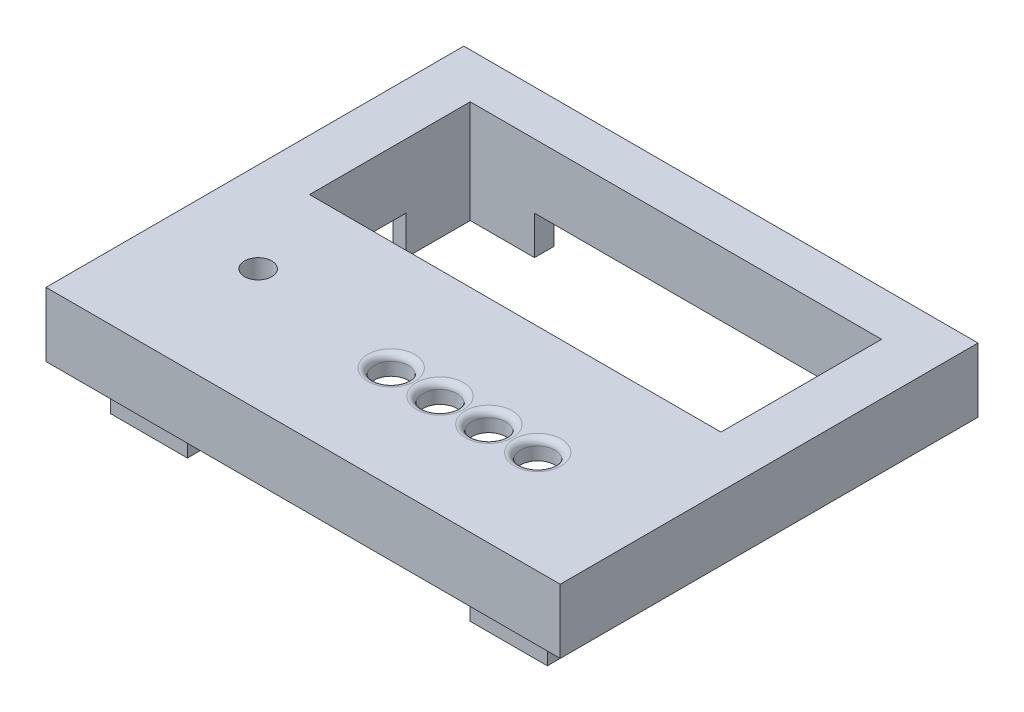
SolidWorks part; units mm, degrees
ref_plane "Front Plane" through (0, 0, 0) normal (0, 0, 1) x (1, 0, 0)
ref_plane "Top Plane" through (0, 0, 0) normal (0, 1, 0) x (1, 0, 0)
ref_plane "Right Plane" through (0, 0, 0) normal (1, 0, 0) x (0, 0, -1)
sketch "Sketch1" plane through (0, 0, 0) normal (0, 1, 0) x (1, 0, 0)
  line L1 (-40, -32.5) -> (40, -32.5)
  line L2 (-40, -32.5) -> (-40, 32.5)
  line L3 (-40, 32.5) -> (40, 32.5)
  line L4 (40, -32.5) -> (40, 32.5)
  line L5 (-40, -32.5) -> (40, 32.5) construction
  line L6 (-40, 32.5) -> (40, -32.5) construction
  line L7 (32, -25.5) -> (-32, -25.5)
  line L8 (32, -25.5) -> (32, 25.5)
  line L9 (32, 25.5) -> (-32, 25.5)
  line L10 (-32, -25.5) -> (-32, 25.5)
  line L11 (32, -25.5) -> (-32, 25.5) construction
  line L12 (32, 25.5) -> (-32, -25.5) construction
  point P0 (0, 0)
  point P6 (0, 0)
  dimension "D1" = 65
  dimension "D2" = 80
  dimension "D3" = 8
  dimension "D4" = 7
extrude "Boss-Extrude1" add sketch "Sketch1" along normal blind 10
sketch "Sketch3" plane through (0, 0, 25.5) normal (0, 0, -1) x (-1, 0, 0)
  line L1 (-32, 10) -> (32, 10)
  line L2 (-32, 10) -> (-32, 7)
  line L3 (-32, 7) -> (32, 7)
  line L4 (32, 10) -> (32, 7)
  line L5 (-32, 10) -> (32, 7) construction
  line L6 (-32, 7) -> (32, 10) construction
  point P4 (0, 8.5)
  point P6 (0, 0)
  point P8 (0, 0)
  point P9 (0, 0)
  point P10 (0, 0)
  point P11 (0, 0)
  dimension "D1" = 3
  dimension "D2" = 64
extrude "Boss-Extrude3" add sketch "Sketch3" along normal blind 26
sketch "Sketch4" plane through (0, 10, 0) normal (0, 1, 0) x (1, 0, 0)
  line L0 (32, 0.5) -> (32, 25.5) construction
  line L1 (-32, 0.5) -> (32, 0.5) construction
  line L2 (-32, 0.5) -> (-32, -25.5) construction
  line L3 (-32, -25.5) -> (32, -25.5) construction
  line L4 (32, 0.5) -> (32, -25.5) construction
  line L5 (-32, 0.5) -> (32, -25.5) construction
  line L6 (-32, -25.5) -> (32, 0.5) construction
  line L7 (-26, 0.5) -> (-26, -25.5) construction
  line L8 (-32, -13.5) -> (32, -13.5) construction
  line L9 (-32, -16.5) -> (32, -16.5) construction
  line L11 (-40, -32.5) -> (40, -32.5) construction
  line L12 (40, -32.5) -> (40, 32.5) construction
  circle A0 centre (-26, -13.5) radius 2.125
  circle A1 centre (20.5, -16.5) radius 2.65
  circle A2 centre (12.9, -16.5) radius 2.65
  circle A3 centre (5.3, -16.5) radius 2.65
  circle A4 centre (-2.3, -16.5) radius 2.65
  point P4 (0, -12.5)
  dimension "D4" = 4.25
  dimension "D6" = 7.6
  dimension "D9" = 5.3
  dimension "D1" = 26
  dimension "D2" = 6
  dimension "D3" = 12
  dimension "D5" = 16
  dimension "D7" = 7.6
  dimension "D8" = 7.6
  dimension "D10" = 19.5
extrude "Cut-Extrude1" cut sketch "Sketch4" against normal up to surface (10 mm away) up to face at (0, 0, 0)
fillet "Fillet1" radius 1 4 edges at (20.5, 10, 19.15) (12.9, 10, 19.15) (5.3, 10, 19.15) (-2.3, 10, 19.15)
sketch "Sketch2" plane through (0, 0, 0) normal (0, -1, 0) x (1, 0, 0)
  line L0 (-32, 25.5) -> (32, 25.5) construction
  line L1 (-22, 25.5) -> (-32, 25.5)
  line L2 (-22, 25.5) -> (-22, 28.5)
  line L3 (-22, 28.5) -> (-34, 28.5)
  line L7 (-32, -25.5) -> (-32, 25.5) construction
  line L9 (-34, 28.5) -> (-34, 15.5)
  line L10 (-34, 15.5) -> (-32, 15.5)
  line L18 (-32, 25.5) -> (-32, 15.5)
  dimension "D1" = 2
  dimension "D2" = 3
  dimension "D3" = 13
  dimension "D4" = 12
extrude "Boss-Extrude2" add sketch "Sketch2" along normal blind 6
mirror "Mirror1" about plane through (0, 0, 0) normal (1, 0, 0) of "Boss-Extrude2" second plane through (0, 0, 0) second plane normal (0, 0, 1)
sketch "Sketch5" plane through (0, 7, 0) normal (0, -1, 0) x (1, 0, 0)
  circle A0 centre (-26, 13.5) radius 3.5
  circle A1 centre (-26, 13.5) radius 2.125
  circle A2 centre (-26, 13.5) radius 2.125 construction
  dimension "D1" = 7
extrude "Boss-Extrude4" add sketch "Sketch5" along normal blind 1.5
